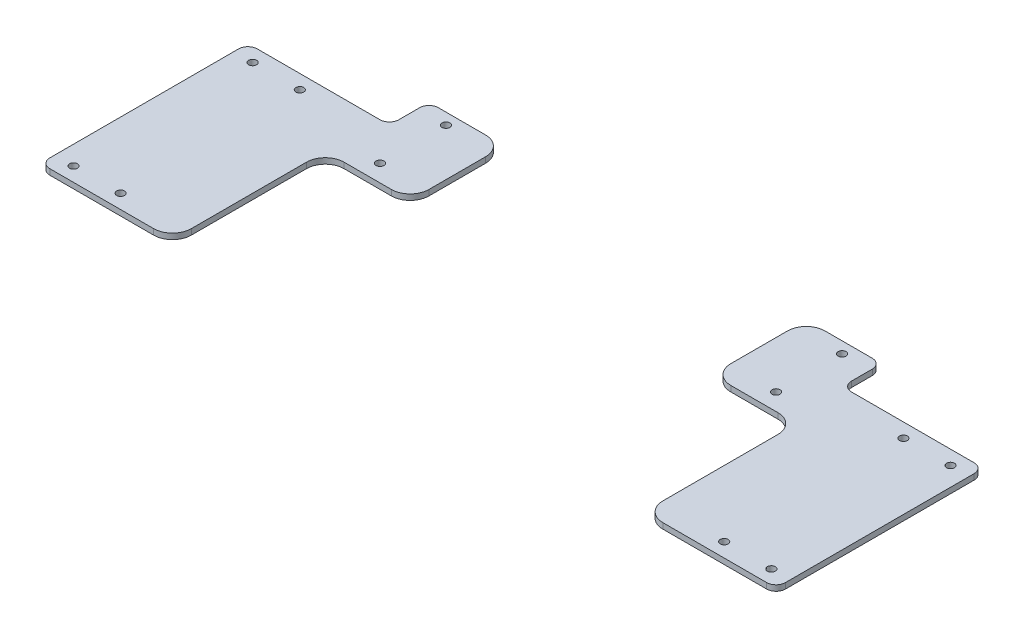
SolidWorks part; units mm, degrees
material "Thornel Mat VMA"
ref_plane "前视基准面" through (0, 0, 0) normal (0, 0, 1) x (1, 0, 0)
ref_plane "上视基准面" through (0, 0, 0) normal (0, 1, 0) x (1, 0, 0)
ref_plane "右视基准面" through (0, 0, 0) normal (1, 0, 0) x (0, 0, -1)
sketch "草图1" plane through (0, 0, 0) normal (0, 1, 0) x (1, 0, 0)
  line L0 (31.5759, -198.8718) -> (31.5759, 46.1282) construction
  line L1 (151.5759, -32.8718) -> (-88.4241, -32.8718)
  line L7 (-88.4241, -198.8718) -> (151.5759, -198.8718)
  line L8 (-88.4241, -198.8718) -> (-88.4241, -32.8718)
  line L10 (151.5759, -198.8718) -> (151.5759, -32.8718)
  line L16 (6.5759, -59.8718) -> (56.5759, -59.8718) construction
  line L18 (6.5759, -34.8718) -> (6.5759, -84.8718) construction
  line L19 (6.5759, -84.8718) -> (56.5759, -84.8718) construction
  line L20 (56.5759, -34.8718) -> (56.5759, -84.8718) construction
  line L21 (151.5759, -94.8718) -> (-88.4241, -94.8718) construction
  line L22 (-88.4241, -49.8718) -> (151.5759, -49.8718) construction
  circle A5 centre (6.5759, -84.8718) radius 1.6 construction
  circle A6 centre (56.5759, -84.8718) radius 1.6 construction
  point P6 (0, -121.2547)
  dimension "D2" = 166
  dimension "D4" = 240
  dimension "D9" = 10
  dimension "D12" = 50
  dimension "D15" = 45
extrude "构型与裁判孔" add sketch "草图1" along normal blind 3 contours L10 L21 L8 L7 region at (31.5759, 0, 115.8718)
sketch "草图4" plane through (0, 3, 0) normal (0, 1, 0) x (1, 0, 0)
  line L0 (-73.4241, -108.8718) -> (-73.4241, -198.8718) construction
  line L1 (77.0759, -32.8718) -> (77.0759, -198.8718) construction
  line L2 (151.5759, -32.8718) -> (-88.4241, -32.8718) construction
  line L3 (-88.4241, -198.8718) -> (-88.4241, -32.8718) construction
  line L4 (31.5759, -32.8718) -> (31.5759, -198.8718) construction
  line L5 (-88.4241, -198.8718) -> (151.5759, -198.8718) construction
  line L6 (-13.9241, -32.8718) -> (-13.9241, -198.8718) construction
  line L7 (-88.4241, -198.8718) -> (151.5759, -198.8718) construction
  line L8 (-88.4241, -198.8718) -> (151.5759, -198.8718) construction
  circle A0 centre (-73.4241, -73.8718) radius 2.1
  circle A1 centre (136.5759, -178.8718) radius 2.1
  circle A2 centre (-73.4241, -108.8718) radius 2.1
  circle A3 centre (-73.4241, -143.8718) radius 2.1
  circle A4 centre (-73.4241, -178.8718) radius 2.1
  circle A5 centre (136.5759, -143.8718) radius 2.1
  circle A6 centre (136.5759, -108.8718) radius 2.1
  circle A7 centre (136.5759, -73.8718) radius 2.1
  circle A8 centre (-73.4241, -38.8718) radius 2.1
  circle A9 centre (136.5759, -38.8718) radius 2.1
  circle A10 centre (77.0759, -188.8718) radius 1.55
  circle A11 centre (-13.9241, -188.8718) radius 1.55
  circle A12 centre (77.0759, -153.8718) radius 1.55
  circle A13 centre (-13.9241, -153.8718) radius 1.55
  dimension "D2" = 20
  dimension "D5" = 35
  dimension "D6" = 35
  dimension "D7" = 35
  dimension "D3" = 4.2
  dimension "D4" = 35
  dimension "D8" = 3.1
  dimension "D9" = 10
  dimension "D10" = 35
  dimension "D1" = 15
  dimension "D11" = 91
extrude "切除-拉伸3" cut sketch "草图4" against normal through all
sketch "草图5" plane through (0, 3, 0) normal (0, 1, 0) x (1, 0, 0)
  line L0 (71.0759, -57.8718) -> (-7.9241, -57.8718)
  line L1 (71.0759, -57.8718) -> (71.0759, -102.8718)
  line L2 (71.0759, -102.8718) -> (-7.9241, -102.8718)
  line L3 (-7.9241, -57.8718) -> (-7.9241, -102.8718)
  line L4 (71.0759, -57.8718) -> (-7.9241, -102.8718) construction
  line L5 (71.0759, -102.8718) -> (-7.9241, -57.8718) construction
  line L6 (31.5759, -32.8718) -> (31.5759, -104.1535) construction
  line L7 (71.0759, -80.3718) -> (-7.9241, -80.3718) construction
  line L8 (31.5759, -57.8718) -> (31.5759, -102.8718) construction
  line L9 (151.5759, -32.8718) -> (-88.4241, -32.8718) construction
  line L10 (91.0759, -100.3718) -> (91.0759, -60.3718) construction
  line L11 (86.0759, -100.3718) -> (86.0759, -60.3718)
  line L12 (96.0759, -100.3718) -> (96.0759, -60.3718)
  line L13 (31.5759, -102.8718) -> (31.5759, -198.8718) construction
  line L16 (-88.4241, -198.8718) -> (151.5759, -198.8718) construction
  line L17 (1.5759, -124.8718) -> (61.5759, -124.8718) construction
  line L18 (1.5759, -117.8718) -> (61.5759, -117.8718)
  line L19 (1.5759, -131.8718) -> (21.5759, -131.8718)
  line L20 (41.5759, -131.8718) -> (61.5759, -131.8718)
  line L21 (-73.4241, -143.8718) -> (136.5759, -143.8718) construction
  circle A0 centre (-5.4241, -51.8718) radius 1.55
  circle A1 centre (68.5759, -51.8718) radius 1.55
  circle A2 centre (68.5759, -108.8718) radius 1.55
  circle A3 centre (-5.4241, -108.8718) radius 1.55
  arc A4 (86.0759, -100.3718) -> (96.0759, -100.3718) centre (91.0759, -100.3718) ccw
  arc A5 (96.0759, -60.3718) -> (86.0759, -60.3718) centre (91.0759, -60.3718) ccw
  arc A8 (1.5759, -117.8718) -> (1.5759, -131.8718) centre (1.5759, -124.8718) ccw
  arc A9 (61.5759, -131.8718) -> (61.5759, -117.8718) centre (61.5759, -124.8718) ccw
  arc A10 (21.5759, -131.8718) -> (41.5759, -131.8718) centre (31.5759, -131.8718) ccw
  circle A11 centre (-45.4241, -143.8718) radius 10
  circle A12 centre (-73.4241, -143.8718) radius 2.1 construction
  circle A13 centre (108.5759, -143.8718) radius 10
  point P1 (110.5236, -62.9669)
  point P23 (91.0759, -80.3718)
  point P33 (31.5759, -124.8718)
  dimension "D3" = 3.1
  dimension "D7" = 5
  dimension "D10" = 7
  dimension "D13" = 20
  dimension "D14" = 28
  dimension "D1" = 79
  dimension "D2" = 45
  dimension "D4" = 37
  dimension "D5" = 28.5
  dimension "D6" = 25
  dimension "D8" = 40
  dimension "D9" = 15
  dimension "D11" = 60
  dimension "D12" = 15
extrude "切除-拉伸4" cut sketch "草图5" against normal through all
sketch "草图6" plane through (0, 0, 0) normal (0, 1, 0) x (1, 0, 0)
  line L0 (-63.0381, -108.8718) -> (146.9619, -108.8718) construction
  line L1 (-88.4241, -53.8718) -> (-163.4241, -53.8718)
  line L2 (-88.4241, -198.8718) -> (-88.4241, -32.8718) construction
  line L3 (-163.4241, -53.8718) -> (-163.4241, -163.8718)
  line L4 (-73.4241, -108.8718) -> (136.5759, -108.8718) construction
  line L5 (-88.4241, -53.8718) -> (-88.4241, -163.8718)
  line L6 (-88.4241, -163.8718) -> (-163.4241, -163.8718)
  line L7 (31.5759, -32.8718) -> (31.5759, -198.8718) construction
  line L8 (151.5759, -32.8718) -> (-88.4241, -32.8718) construction
  line L9 (-88.4241, -198.8718) -> (151.5759, -198.8718) construction
  line L10 (151.5759, -53.8718) -> (151.5759, -163.8718)
  line L11 (151.5759, -163.8718) -> (226.5759, -163.8718)
  line L12 (226.5759, -53.8718) -> (226.5759, -163.8718)
  line L13 (151.5759, -53.8718) -> (226.5759, -53.8718)
  line L14 (-153.4241, -53.8718) -> (-153.4241, -163.8718) construction
  line L15 (-128.4241, -53.8718) -> (-128.4241, -163.8718) construction
  line L16 (-153.4241, -61.3718) -> (-128.4241, -61.3718) construction
  circle A0 centre (-153.4241, -61.3718) radius 2.1
  circle A1 centre (-153.4241, -156.3718) radius 2.1
  circle A2 centre (216.5759, -156.3718) radius 2.1
  circle A3 centre (216.5759, -61.3718) radius 2.1
  circle A4 centre (-128.4241, -61.3718) radius 2.1
  circle A5 centre (-128.4241, -156.3718) radius 2.1
  circle A6 centre (191.5759, -156.3718) radius 2.1
  circle A7 centre (191.5759, -61.3718) radius 2.1
  point P15 (-88.4241, -108.8718)
  point P16 (-163.4241, -108.8718)
  dimension "D4" = 95
  dimension "D6" = 4.2
  dimension "D7" = 4.2
  dimension "D1" = 75
  dimension "D2" = 55
  dimension "D3" = 10
  dimension "D5" = 25
extrude "凸台-拉伸1" add sketch "草图6" along normal blind 3
fillet "圆角1" radius 5 18 edges at (71.0759, 1.5, 102.8718) (-7.9241, 1.5, 102.8718) (-7.9241, 1.5, 57.8718) (71.0759, 1.5, 57.8718) (151.5759, 1.5, 32.8718) (-88.4241, 1.5, 32.8718) (151.5759, 1.5, 53.8718) (151.5759, 1.5, 163.8718) (-88.4241, 1.5, 163.8718) (-88.4241, 1.5, 53.8718) (226.5759, 1.5, 53.8718) (226.5759, 1.5, 163.8718) (151.5759, 1.5, 198.8718) (-88.4241, 1.5, 198.8718) (-163.4241, 1.5, 53.8718) (-163.4241, 1.5, 163.8718) (41.5759, 1.5, 131.8718) (21.5759, 1.5, 131.8718)
sketch "草图7" plane through (0, 3, 0) normal (0, 1, 0) x (1, 0, 0)
  line L0 (146.5759, -32.8718) -> (-83.4241, -32.8718) construction
  line L1 (-48.4241, -32.8718) -> (-48.4241, -82.8718)
  line L2 (-88.4241, -48.8718) -> (-88.4241, -37.8718) construction
  line L3 (-93.4241, -82.8718) -> (-48.4241, -82.8718)
  line L4 (-83.4241, -198.8718) -> (146.5759, -198.8718) construction
  line L5 (31.5759, -198.8718) -> (31.5759, 61.0332) construction
  line L6 (156.5759, -82.8718) -> (111.5759, -82.8718)
  line L7 (151.7733, -149.2908) -> (156.5759, -82.8718)
  line L8 (111.5759, -32.8718) -> (111.5759, -82.8718)
  line L10 (-48.4241, -32.8718) -> (111.5759, -32.8718)
  line L11 (-93.4241, -82.8718) -> (156.5759, -82.8718)
  line L12 (-93.4241, -82.8718) -> (-93.4241, -208.1915)
  line L13 (-93.4241, -208.1915) -> (156.5759, -208.1915)
  line L14 (156.5759, -82.8718) -> (156.5759, -208.1915)
  line L19 (-48.4241, -32.8718) -> (-48.4241, -82.8718)
  line L20 (-48.4241, -82.8718) -> (111.5759, -82.8718)
  line L21 (111.5759, -32.8718) -> (111.5759, -82.8718)
  point P0 (-92.6438, -129.6631)
  dimension "D1" = 50
  dimension "D2" = 40
  dimension "D3" = 0
extrude "切除-拉伸5" cut sketch "草图7" against normal blind 10 contours L5 | L5 | L5 L11 L8 | L11 L5 L1 | L14 L7 L6 L11 L3 L12 L13 region at (31.5759, 3, 57.8718) region at (31.5759, 3, 145.5316)
fillet "圆角2" radius 10 4 edges at (-48.4241, 1.5, 32.8718) (-48.4241, 1.5, 82.8718) (-93.4241, 1.5, 163.8718) (-93.4241, 1.5, 82.8718)
fillet "圆角3" radius 10 4 edges at (156.5759, 1.5, 163.8718) (156.5759, 1.5, 82.8718) (111.5759, 1.5, 82.8718) (111.5759, 1.5, 32.8718)
